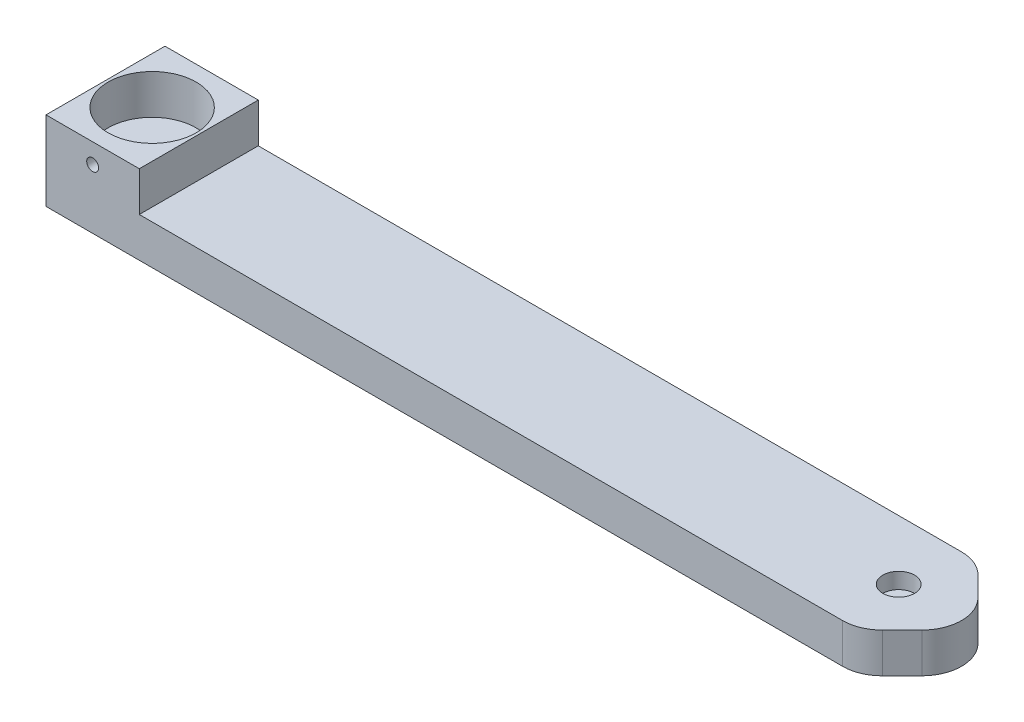
SolidWorks part; units mm, degrees
ref_plane "Front Plane" through (0, 0, 0) normal (0, 0, 1) x (1, 0, 0)
ref_plane "Top Plane" through (0, 0, 0) normal (0, 1, 0) x (1, 0, 0)
ref_plane "Right Plane" through (0, 0, 0) normal (1, 0, 0) x (0, 0, -1)
sketch "Sketch1" plane through (0, 0, 0) normal (0, 1, 0) x (1, 0, 0)
  line L1 (-110, -15) -> (110, -15)
  line L2 (-110, -15) -> (-110, 15)
  line L3 (-110, 15) -> (110, 15)
  line L4 (110, -15) -> (110, 15)
  line L5 (-110, -15) -> (110, 15) construction
  line L6 (-110, 15) -> (110, -15) construction
  point P0 (0, 0)
  dimension "D1" = 220
  dimension "D2" = 30
extrude "Boss-Extrude1" add sketch "Sketch1" along normal blind 10
sketch "Sketch2" plane through (0, 10, 0) normal (0, 1, 0) x (1, 0, 0)
  line L0 (-11, 0) -> (11, 0) construction
  line L2 (-86.4763, -15) -> (-110, -15)
  line L3 (-86.4763, -15) -> (-86.4763, 15)
  line L4 (-86.4763, 15) -> (-110, 15)
  line L5 (-110, -15) -> (-110, 15)
  line L6 (-86.4763, -15) -> (-110, 15) construction
  line L7 (-86.4763, 15) -> (-110, -15) construction
  circle A1 centre (-98.2382, 0) radius 11.1
  point P0 (-104.73, 0)
  line M3 (110, 15) -> (-110, 15)
  line M4 (-110, 15) -> (-110, -15)
  line M5 (-110, -15) -> (110, -15)
  dimension "D2" = 22.2
extrude "Boss-Extrude3" add sketch "Sketch2" along normal blind 10 contours L3 A1 M5 M3 M4 region at (-98.2382, 10, 14.6188)
sketch "Sketch4" plane through (0, 10, 0) normal (0, 1, 0) x (1, 0, 0)
  line L0 (-11, 0) -> (11, 0) construction
  line L1 (110, -15) -> (110, 15) construction
  circle A0 centre (90, 0) radius 4
  dimension "D1" = 8
  dimension "D2" = 20
sketch "Sketch6" plane through (0, 0, 15) normal (0, 0, 1) x (1, 0, 0)
  line L0 (-86.4763, 10) -> (-110, 10) construction
  line L1 (-110, 20) -> (-110, 0) construction
  line L2 (-98.2382, 20) -> (-98.2382, 10) construction
  line L3 (-110, 20) -> (-86.4763, 20) construction
  circle A0 centre (-98.2382, 15) radius 1.5
  dimension "D1" = 3
extrude "Cut-Extrude2" cut sketch "Sketch6" against normal blind 10
extrude "Cut-Extrude3" cut sketch "Sketch4" against normal blind 4
sketch "Sketch7" plane through (0, 6, 0) normal (0, 1, 0) x (1, 0, 0)
  circle A0 centre (90, 0) radius 1.5
  dimension "D1" = 3
extrude "Cut-Extrude4" cut sketch "Sketch7" against normal blind 14
sketch "Sketch8" plane through (0, 10, 0) normal (0, 1, 0) x (1, 0, 0)
  line L0 (95, 15) -> (110, 0)
  line L1 (110, 15) -> (-86.4763, 15) construction
  line L2 (110, -15) -> (110, 15) construction
  line L4 (110, 0) -> (95, -15)
  line L5 (-86.4763, -15) -> (110, -15) construction
  line L6 (95, -15) -> (110, -15)
  line L7 (110, -15) -> (110, 0)
  line L8 (110, 0) -> (110, 15)
  line L9 (110, 15) -> (95, 15)
  line L11 (110, 15) -> (95, 15) construction
  line L12 (110, 15) -> (110, 0) construction
  line L13 (110, 0) -> (95, 0) construction
  line L14 (95, 15) -> (95, 0) construction
  point P12 (0, 0)
  point P16 (0, 0)
  point P17 (0, 0)
  line M11 (-86.4763, -15) -> (110, -15)
  line M12 (110, -15) -> (110, 15)
  line M13 (110, 15) -> (-86.4763, 15)
extrude "Cut-Extrude5" cut sketch "Sketch8" against normal blind 10 contours L4 M12 M11 | L0 M13 M12 region at (105, 10, -10) region at (105, 10, 10)
fillet "Fillet1" radius 10 3 edges at (95, 5, -15) (110, 5, 0) (95, 5, 15)
